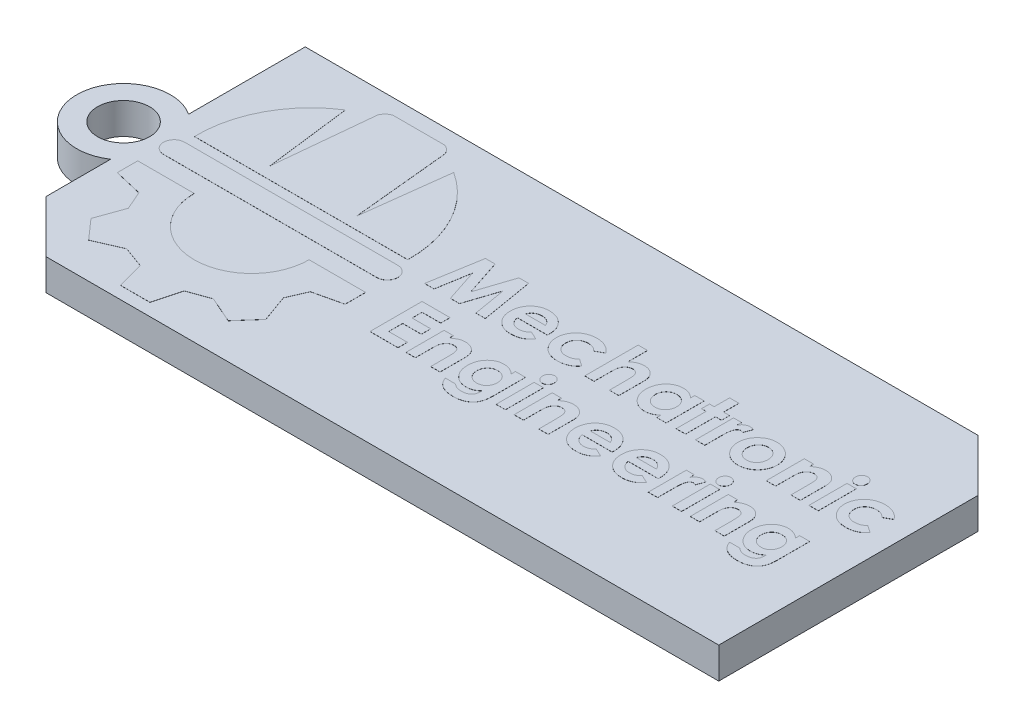
SolidWorks part; units mm, degrees
ref_plane "Front Plane" through (0, 0, 0) normal (0, 0, 1) x (1, 0, 0)
ref_plane "Top Plane" through (0, 0, 0) normal (0, 1, 0) x (1, 0, 0)
ref_plane "Right Plane" through (0, 0, 0) normal (1, 0, 0) x (0, 0, -1)
sketch "Sketch1" plane through (0, 0, 0) normal (0, 1, 0) x (1, 0, 0)
  line L0 (29.3475, 202.1204) -> (256.0142, 202.1204) construction
  line L2 (14.2735, 15.8084) -> (8.8493, 15.8084)
  line L3 (8.8493, 15.8084) -> (8.8493, 13.8471)
  line L4 (8.8493, 13.8471) -> (11.5612, 13.2114)
  line L5 (11.5612, 13.2114) -> (12.3459, 11.4101)
  line L6 (12.3459, 11.4101) -> (11.3967, 8.7702)
  line L7 (11.3967, 8.7702) -> (13.0877, 6.8539)
  line L8 (13.0877, 6.8539) -> (15.6256, 7.9627)
  line L9 (15.6256, 7.9627) -> (17.691, 7.2201)
  line L10 (17.691, 7.2201) -> (18.3856, 4.6254)
  line L11 (18.3856, 4.6254) -> (21.2024, 4.6254)
  line L12 (30.0366, 20.5555) -> (9.5513, 20.5555)
  line L13 (30.0366, 19.609) -> (9.5513, 19.609)
  line L15 (30.0366, 17.5863) -> (9.5513, 17.5863)
  line L17 (14.5912, 30.0156) -> (15.6256, 21.6943)
  line L18 (15.6256, 21.6943) -> (16.5621, 31.1544)
  line L19 (22.2813, 31.8611) -> (17.3066, 31.8611)
  line L20 (23.9624, 21.6943) -> (23.0259, 31.1544)
  line L21 (24.9967, 30.0156) -> (23.9624, 21.6943)
  line L22 (21.8969, 7.2201) -> (21.2024, 4.6254)
  line L23 (23.9624, 7.9627) -> (21.8969, 7.2201)
  line L24 (26.5003, 6.8539) -> (23.9624, 7.9627)
  line L25 (28.1912, 8.7702) -> (26.5003, 6.8539)
  line L26 (27.242, 11.4101) -> (28.1912, 8.7702)
  line L27 (28.0267, 13.2114) -> (27.242, 11.4101)
  line L28 (30.7386, 13.8471) -> (28.0267, 13.2114)
  line L29 (30.7386, 15.8084) -> (30.7386, 13.8471)
  line L30 (25.3145, 15.8084) -> (30.7386, 15.8084)
  arc A0 (14.2735, 15.8084) -> (25.3145, 15.8084) centre (19.794, 15.8084) ccw
  arc A1 (9.5513, 19.609) -> (9.5513, 17.5863) centre (9.5513, 18.5977) ccw
  arc A2 (16.5621, 31.1544) -> (17.3066, 31.8611) centre (17.6947, 30.7068) cw
  arc A3 (14.5912, 30.0156) -> (9.5513, 20.5555) centre (20.4672, 20.8126) ccw
  arc A4 (24.9967, 30.0156) -> (30.0366, 20.5555) centre (19.1207, 20.8126) cw
  arc A5 (23.0259, 31.1544) -> (22.2813, 31.8611) centre (21.8933, 30.7068) ccw
  arc A6 (30.0366, 19.609) -> (30.0366, 17.5863) centre (30.0366, 18.5977) cw
  text T0 "<b>Mechatronic</b>" font "Century Gothic" height 5
  text T1 "<b>Engineering</b>" font "Century Gothic" height 5
  point P39 (19.794, 20.5555)
extrude "Boss-Extrude5" add sketch "Sketch1" along normal blind 0.01
sketch "Sketch4" plane through (0, 0, 0) normal (0, -1, 0) x (1, 0, 0)
  line L1 (7.4061, -33.3446) -> (77.0362, -33.3446)
  line L2 (7.4061, -33.3446) -> (7.4061, -3.4394)
  line L3 (7.4061, -3.4394) -> (77.0362, -3.4394)
  line L4 (77.0362, -33.3446) -> (77.0362, -3.4394)
extrude "Boss-Extrude6" add sketch "Sketch4" along normal blind 3
chamfer "Chamfer1" distance 5 angle 45 2 edges at (7.4061, -1.5, -3.4394) (77.0362, -1.5, -33.3446)
sketch "Sketch5" plane through (0, 0, 0) normal (0, 1, 0) x (1, 0, 0)
  circle A0 centre (4.9061, 18.392) radius 2.5
  circle A1 centre (4.9061, 18.392) radius 4.5
  dimension "D1" = 2
extrude "Boss-Extrude9" add sketch "Sketch5" against normal blind 3
